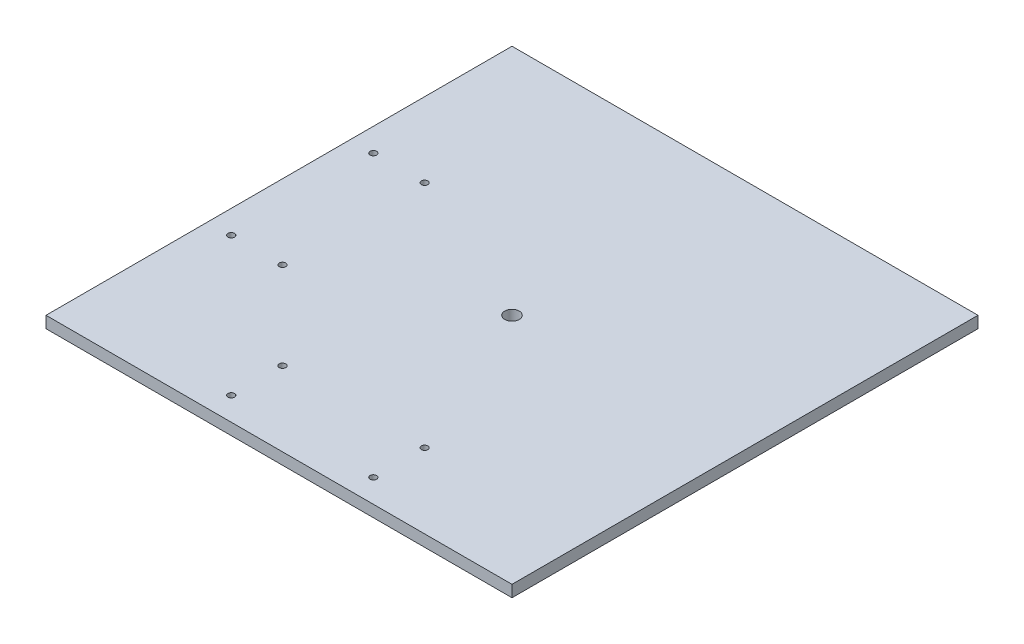
SolidWorks part; units mm, degrees
material "Acrylic (Medium-high impact)"
ref_plane "Front Plane" through (0, 0, 0) normal (0, 0, 1) x (1, 0, 0)
ref_plane "Top Plane" through (0, 0, 0) normal (0, 1, 0) x (1, 0, 0)
ref_plane "Right Plane" through (0, 0, 0) normal (1, 0, 0) x (0, 0, -1)
ref_axis "Axis1" through (0, -0.635, 0) along (0, 1, 0)
ref_axis "Axis2" through (-279.4, 0, 0) along (1, 0, 0)
ref_axis "Axis3" through (0, 0, 279.4) along (0, 0, -1)
sketch "Sketch1" plane through (0, 0, 0) normal (0, 1, 0) x (1, 0, 0)
  line L1 (-254, -254) -> (254, -254)
  line L2 (-254, -254) -> (-254, 254)
  line L3 (-254, 254) -> (254, 254)
  line L4 (254, -254) -> (254, 254)
  line L5 (-254, -254) -> (254, 254) construction
  line L6 (-254, 254) -> (254, -254) construction
  point P0 (0, 0)
  dimension "D1" = 508
  dimension "D2" = 508
extrude "Boss-Extrude1" add sketch "Sketch1" along normal blind 12.7
hole_wizard "K (0.281) Diameter Hole1" positions "Sketch5" profile "Sketch6" hole size "K" standard "ANSI Inch" end condition up to next
sketch "Sketch5" plane through (0, 12.7, 0) normal (0, 1, 0) x (1, 0, 0)
  line L1 (77.47, -172.72) -> (-77.47, -172.72) construction
  line L3 (0, -279.4) -> (0, 279.4) construction
  line L4 (-172.72, 77.47) -> (-172.72, -77.47) construction
  line L6 (-279.4, 0) -> (279.4, 0) construction
  line L7 (-254, 254) -> (-254, -254) construction
  line L8 (-254, -254) -> (254, -254) construction
  point P0 (-77.47, -228.6)
  point P2 (-77.47, -172.72)
  point P4 (77.47, -172.72)
  point P6 (77.47, -228.6)
  point P8 (-228.6, -77.47)
  point P10 (-172.72, -77.47)
  point P12 (-172.72, 77.47)
  point P14 (-228.6, 77.47)
  point P32 (0, -172.72)
  point P42 (-172.72, 0)
  dimension "D1" = 55.88
  dimension "D2" = 154.94
  dimension "D3" = 55.88
  dimension "D4" = 154.94
  dimension "D5" = 25.4
  dimension "D6" = 25.4
sketch "Sketch6" plane through (-77.47, 12.7, 228.6) normal (1, 0, 0) x (0, 0, 1)
  line L0 (0, 0) -> (0, 12.7)
  line L1 (0, 12.7) -> (3.5687, 12.7)
  line L2 (3.5687, 12.7) -> (3.5687, 0)
  line L5 (3.5687, 0) -> (0, 0)
  line L11 (0, -6.35) -> (0, 107.95) construction
  dimension "Thru Hole Dia." = 7.1374
  dimension "Thru Hole Depth" = 12.7
hole_wizard "5/8 (0.625) Diameter Hole1" positions "Sketch7" profile "Sketch8" hole size "5/8" standard "ANSI Inch"
sketch "Sketch7" plane through (0, 12.7, 0) normal (0, 1, 0) x (1, 0, 0)
  point P0 (0, 0)
sketch "Sketch8" plane through (0, 12.7, 0) normal (1, 0, 0) x (0, 0, 1)
  line L0 (0, 0) -> (0, 30.1693)
  line L1 (0, 30.1693) -> (7.9375, 25.4)
  line L2 (7.9375, 25.4) -> (7.9375, 0)
  line L5 (7.9375, 0) -> (0, 0)
  line L10 (0, 30.1693) -> (-7.9375, 25.4) construction
  line L11 (0, -6.35) -> (0, 107.95) construction
  dimension "Hole Dia." = 15.875
  dimension "Hole Depth" = 25.4
  dimension "Drill Angle" = 118
